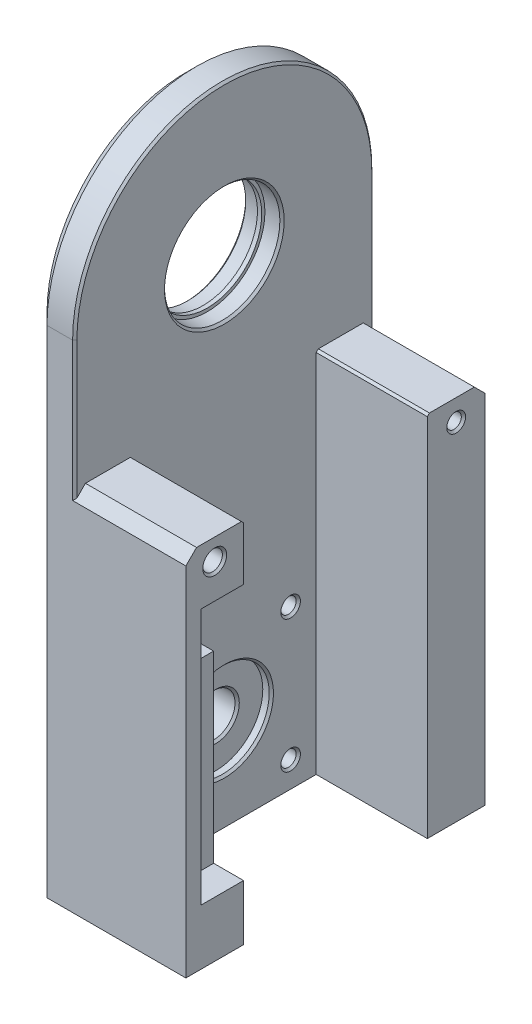
SolidWorks part; units mm, degrees
ref_plane "Ebene vorne" through (0, 0, 0) normal (0, 0, 1) x (1, 0, 0)
ref_plane "Ebene oben" through (0, 0, 0) normal (0, 1, 0) x (1, 0, 0)
ref_plane "Ebene rechts" through (0, 0, 0) normal (1, 0, 0) x (0, 0, -1)
sketch "Sketch2" plane through (0, 0, 0) normal (1, 0, 0) x (0, 0, -1)
  line L1 (0, 0) -> (70, 0)
  line L2 (0, 0) -> (0, 86)
  line L3 (0, 86) -> (70, 86)
  line L4 (70, 0) -> (70, 86)
  line L5 (0, 0) -> (70, 86) construction
  line L6 (0, 86) -> (70, 0) construction
  line L7 (0, 86) -> (70, 86)
  line L8 (0, 86) -> (0, 116)
  line L9 (0, 116) -> (70, 116)
  line L10 (70, 86) -> (70, 116)
  line L11 (0, 86) -> (70, 116) construction
  line L12 (0, 116) -> (70, 86) construction
  circle A0 centre (35, 116) radius 35
  circle A1 centre (35, 116) radius 12.75
  point P4 (35, 43)
  point P9 (35, 101)
  dimension "D4" = 70
  dimension "D5" = 25.5
  dimension "D2" = 86
  dimension "D3" = 30
extrude "Boss-Extrude1" add sketch "Sketch2" along normal blind 35 contours A0 L3 L2 L1 L4 | L7 A0 region at (0, 42.1521, -35) region at (0, 83.9872, -35)
sketch "Sketch3" plane through (35, 0, 0) normal (1, 0, 0) x (0, 0, -1)
  line L1 (0, 86) -> (70, 86) construction
  line L2 (0, 0) -> (70, 0) construction
  line L8 (35, 0) -> (35, 86) construction
  line L9 (13.5, 0) -> (56.5, 0)
  line L10 (13.5, 0) -> (13.5, 43)
  line L11 (13.5, 43) -> (56.5, 43)
  line L12 (56.5, 0) -> (56.5, 43)
  line L13 (13.5, 0) -> (56.5, 43) construction
  line L14 (13.5, 43) -> (56.5, 0) construction
  line L15 (56.5, 43) -> (13.5, 43)
  line L16 (56.5, 43) -> (56.5, 86)
  line L17 (56.5, 86) -> (13.5, 86)
  line L18 (13.5, 43) -> (13.5, 86)
  line L19 (56.5, 43) -> (13.5, 86) construction
  line L20 (56.5, 86) -> (13.5, 43) construction
  line L21 (13.5, 73) -> (3.5, 73)
  line L22 (13.5, 73) -> (13.5, 56)
  line L23 (13.5, 56) -> (3.5, 56)
  line L24 (3.5, 73) -> (3.5, 56)
  line L25 (13.5, 73) -> (3.5, 56) construction
  line L26 (13.5, 56) -> (3.5, 73) construction
  circle A0 centre (35, 21.5) radius 11
  circle A1 centre (35, 21.5) radius 5
  point P15 (35, 21.5)
  point P19 (35, 64.5)
  point P26 (8.5, 64.5)
  line M14 (70, 86) -> (0, 86)
  line M16 (0, 0) -> (70, 0)
  dimension "D3" = 22
  dimension "D4" = 10
  dimension "D5" = 10
  dimension "D6" = 17
extrude "Cut-Extrude1" cut sketch "Sketch3" against normal offset from surface (26 mm away) 9 contours L11 M14 | A0 A1 | A1 | L11 A0 M16 | L21 L24 L23 L18 region at (35, 21.5, -14.1081) region at (35, 64.5, -35) region at (35, 64.5, -8.5) region at (35, 21.5, -24.3111) region at (35, 21.5, -35) up to face at (0, 43, -35)
extrude "Boss-Extrude2" add sketch "Sketch2<3>" along normal up to surface (9 mm away) contours L9 A0 L7 | A0 L3 L10 | A0 L8 L3 | L9 A0 region at (0, 93.0889, -4.7772) region at (0, 93.0889, -65.2228) region at (0, 100.9401, -35) region at (0, 132.2994, -35) up to face at (9, 53.75, -21.75)
sketch "Sketch2<3>" plane through (0, 0, 0) normal (1, 0, 0) x (0, 0, -1) same geometry as "Sketch2"
extrude "Cut-Extrude2" cut sketch "Sketch3<3>" against normal offset from surface (28 mm away) 2 contours A0 A1 | A1 region at (35, 21.5, -24.3111) region at (35, 21.5, -35) up to face at (9, 72.4167, -26.1667) offset beyond the face yes
sketch "Sketch3<3>" plane through (35, 0, 0) normal (1, 0, 0) x (0, 0, -1) same geometry as "Sketch3"
extrude "Cut-Extrude3" cut sketch "Sketch3<4>" against normal through all contours A1 region at (35, 21.5, -35)
sketch "Sketch3<4>" plane through (35, 0, 0) normal (1, 0, 0) x (0, 0, -1) same geometry as "Sketch3"
sketch "Sketch15" plane through (9, 0, 0) normal (1, 0, 0) x (0, 0, -1)
  circle A0 centre (35, 116) radius 13.5
  dimension "D1" = 27
extrude "Cut-Extrude4" cut sketch "Sketch15" against normal blind 4
ref_plane "Plane1" through (4.5, 0, 0) normal (1, 0, 0) x (0, 0, -1)
mirror "Mirror1" about plane through (4.5, 0, 0) normal (1, 0, 0) of "Cut-Extrude4"
hole_wizard "CBORE for M3 Hex Socket Head Cap Screw1" positions "Sketch4" profile "Sketch5" counterbore size "M3" standard "DIN" end condition through all
sketch "Sketch4" plane through (0, 0, 0) normal (-1, 0, 0) x (0, 0, 1)
  line L1 (-50.5, 6) -> (-19.5, 6)
  line L2 (-50.5, 6) -> (-50.5, 37)
  line L3 (-50.5, 37) -> (-19.5, 37)
  line L4 (-19.5, 6) -> (-19.5, 37)
  line L5 (-50.5, 6) -> (-19.5, 37) construction
  line L6 (-50.5, 37) -> (-19.5, 6) construction
  point P0 (-35, 21.5)
  point P1 (-19.5, 37)
  point P4 (-50.5, 6)
  point P5 (-50.5, 37)
  point P6 (-19.5, 6)
  dimension "D1" = 31
sketch "Sketch5" plane through (0, 6, -19.5) normal (0, 1, 0) x (0, 0, 1)
  line L0 (0, 0) -> (0, 35)
  line L1 (0, 35) -> (1.8, 35)
  line L3 (1.8, 35) -> (1.8, 3.4)
  line L4 (1.8, 3.4) -> (3.25, 3.4)
  line L5 (3.25, 3.4) -> (3.25, 0)
  line L7 (3.25, 0) -> (0, 0)
  line L11 (0, -6.35) -> (0, 107.95) construction
  dimension "Thru Hole Dia." = 3.6
  dimension "Thru Hole Depth" = 35
  dimension "C'Bore Dia." = 6.5
  dimension "C'Bore Depth" = 3.4
hole_wizard "Ø4.6 (4.6) Diameter Hole1" positions "Sketch8" profile "Sketch9" hole size "Ø4.6" standard "DIN"
sketch "Sketch8" plane through (0, 0, 0) normal (0, -1, 0) x (-1, 0, 0)
  line L0 (-35, 70) -> (-35, 0) construction
  line L1 (-35, 0) -> (0, 0) construction
  line L2 (-35, 0) -> (-35, 13.5) construction
  line L5 (-65.5, 6.5) -> (-4.5, 6.5)
  line L6 (-65.5, 6.5) -> (-65.5, 63.5)
  line L7 (-65.5, 63.5) -> (-4.5, 63.5)
  line L8 (-4.5, 6.5) -> (-4.5, 63.5)
  line L9 (-65.5, 6.5) -> (-4.5, 63.5) construction
  line L10 (-65.5, 63.5) -> (-4.5, 6.5) construction
  line L11 (-35, 70) -> (0, 70) construction
  line L12 (0, 0) -> (0, 70) construction
  point P9 (-35, 35)
  point P10 (-4.5, 63.5)
  point P15 (-4.5, 6.5)
  point P89 (-4.5, 35)
  dimension "D1" = 6.5
  dimension "D2" = 4.5
sketch "Sketch9" plane through (4.5, 0, -35) normal (1, 0, 0) x (0, 0, -1)
  line L0 (0, 0) -> (0, 7.382)
  line L1 (0, 7.382) -> (2.3, 6)
  line L2 (2.3, 6) -> (2.3, 0)
  line L5 (2.3, 0) -> (0, 0)
  line L10 (0, 7.382) -> (-2.3, 6) construction
  line L11 (0, -6.35) -> (0, 107.95) construction
  dimension "Hole Dia." = 4.6
  dimension "Hole Depth" = 6
  dimension "Drill Angle" = 118
hole_wizard "CBORE for M3 Hex Socket Head Cap Screw2" positions "Sketch10" profile "Sketch11" counterbore size "M3" standard "DIN" end condition through all
sketch "Sketch10" plane through (0, 0, 0) normal (-1, 0, 0) x (0, 0, 1)
  line L0 (-56.5, 86) -> (-70, 86) construction
  line L1 (-56.5, 86) -> (-70, 86)
  line L2 (-63.25, 86) -> (-63.25, 81) construction
  point P4 (-63.25, 81)
  dimension "D1" = 5
sketch "Sketch11" plane through (0, 81, -63.25) normal (0, 1, 0) x (0, 0, 1)
  line L0 (0, 0) -> (0, 35)
  line L1 (0, 35) -> (1.7, 35)
  line L3 (1.7, 35) -> (1.7, 21.4)
  line L4 (1.7, 21.4) -> (3.25, 21.4)
  line L5 (3.25, 21.4) -> (3.25, 0)
  line L7 (3.25, 0) -> (0, 0)
  line L11 (0, -6.35) -> (0, 107.95) construction
  dimension "Thru Hole Dia." = 3.4
  dimension "Thru Hole Depth" = 35
  dimension "C'Bore Dia." = 6.5
  dimension "C'Bore Depth" = 21.4
hole_wizard "Ø4.6 (4.6) Diameter Hole2" positions "Sketch12" profile "Sketch14" hole size "Ø4.6" standard "DIN"
sketch "Sketch12" plane through (35, 0, 0) normal (1, 0, 0) x (0, 0, -1)
  line L0 (6.75, 86) -> (6.75, 81) construction
  line L1 (0, 86) -> (13.5, 86) construction
  point P1 (6.75, 81)
  dimension "D1" = 5
sketch "Sketch14" plane through (35, 81, -6.75) normal (0, 1, 0) x (0, 0, -1)
  line L0 (0, 0) -> (0, 7.382)
  line L1 (0, 7.382) -> (2.3, 6)
  line L2 (2.3, 6) -> (2.3, 0)
  line L5 (2.3, 0) -> (0, 0)
  line L10 (0, 7.382) -> (-2.3, 6) construction
  line L11 (0, -6.35) -> (0, 107.95) construction
  dimension "Hole Dia." = 4.6
  dimension "Hole Depth" = 6
  dimension "Drill Angle" = 118
hole_wizard "Ø4.6 (4.6) Diameter Hole3" positions "Sketch18" profile "Sketch17" hole size "Ø4.6" standard "DIN"
sketch "Sketch18" plane through (0, 0, 0) normal (-1, 0, 0) x (0, 0, 1)
  line L0 (-35, 21.5) -> (-35, 116) construction
  point P9 (-10, 68.75)
  point P18 (-35, 68.75)
  point P20 (-60, 68.75)
  dimension "D1" = 25
sketch "Sketch17" plane through (0, 68.75, -60) normal (0, 1, 0) x (0, 0, 1)
  line L0 (0, 0) -> (0, 6.382)
  line L1 (0, 6.382) -> (2.3, 5)
  line L2 (2.3, 5) -> (2.3, 0)
  line L5 (2.3, 0) -> (0, 0)
  line L10 (0, 6.382) -> (-2.3, 5) construction
  line L11 (0, -6.35) -> (0, 107.95) construction
  dimension "Hole Dia." = 4.6
  dimension "Hole Depth" = 5
  dimension "Drill Angle" = 118
sketch "Sketch19" plane through (0, 0, -13.5) normal (0, 0, -1) x (-1, 0, 0)
  line L1 (-35, 56) -> (-28, 56)
  line L2 (-35, 56) -> (-35, 13)
  line L3 (-35, 13) -> (-28, 13)
  line L4 (-28, 56) -> (-28, 13)
  line L5 (-35, 56) -> (-28, 13) construction
  line L6 (-35, 13) -> (-28, 56) construction
  point P4 (-31.5, 34.5)
  dimension "D1" = 7
  dimension "D2" = 43
extrude "Cut-Extrude5" cut sketch "Sketch19" against normal up to surface (10 mm away) up to face at (22, 64.5, -3.5)
chamfer "2,5mm Chamfer1" distance 2.5 angle 45 5 edges at (22, 86, -70) (22, 86, 0) (0, 58, 0) (0, 151, -35) (0, 58, -70)
chamfer "0,5mm Chamfer2" distance 0.5 angle 45 26 edges at (0, 21.5, -40) (7, 21.5, -40) (9, 21.5, -46) (4.5, 0, -8.8) (4.5, 0, -37.3) (4.5, 0, -65.8) (9, 6, -21.3) (9, 6, -52.3) (9, 37, -52.3) (9, 37, -21.3) (35, 81, -61.55) (35, 81, -9.05) (9, 99.75, -70) (9, 99.75, 0) (9, 151, -35) (0, 6, -16.25) (0, 6, -47.25) (0, 37, -16.25) (0, 37, -47.25) (0, 81, -60) (22, 86, -56.5) (0, 116, -48.5) (9, 116, -48.5) (0, 68.75, -7.7) (0, 68.75, -57.7) (22, 86, -13.5)
